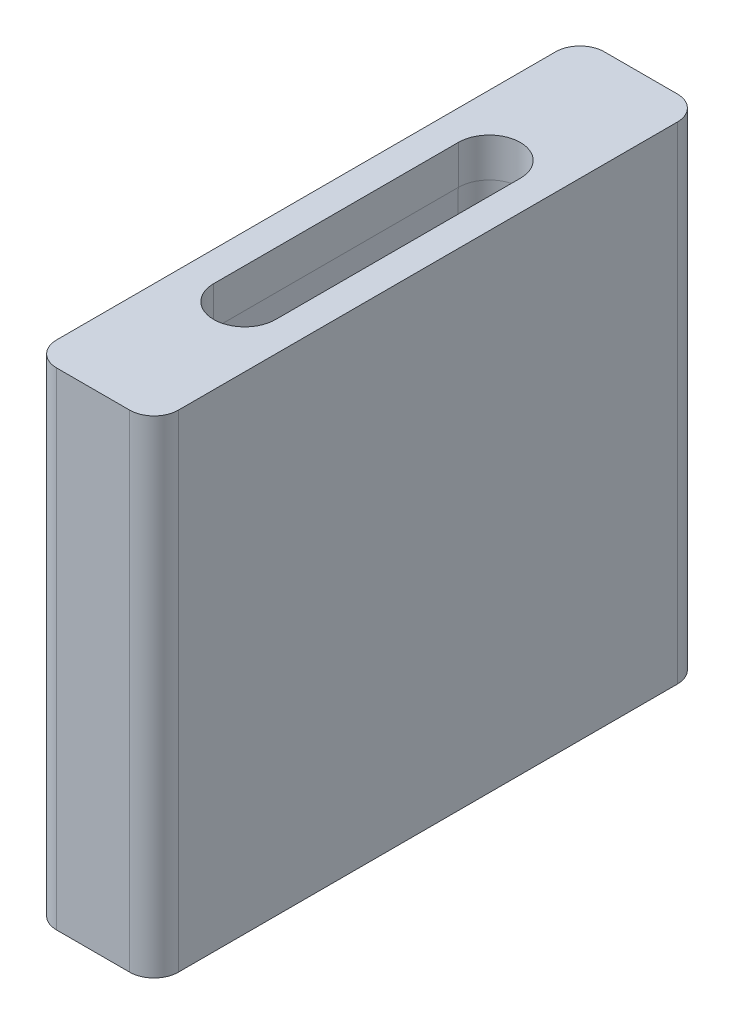
SolidWorks part; units mm, degrees
material "K110"
ref_plane "Front Plane" through (0, 0, 0) normal (0, 0, 1) x (1, 0, 0)
ref_plane "Top Plane" through (0, 0, 0) normal (0, 1, 0) x (1, 0, 0)
ref_plane "Right Plane" through (0, 0, 0) normal (1, 0, 0) x (0, 0, -1)
sketch "Sketch1" plane through (0, 0, 0) normal (0, 1, 0) x (1, 0, 0)
  line L3 (0, -3.5) -> (0, 3.5) construction
  line L4 (-2.62, -3.5) -> (-2.62, 3.5) construction
  line L5 (2.62, -3.5) -> (2.62, 3.5) construction
  line L6 (-3, -22.5) -> (3, -22.5)
  line L7 (-5, -20.5) -> (-5, 20.5)
  line L8 (-3, 22.5) -> (3, 22.5)
  line L9 (5, -20.5) -> (5, 20.5)
  line L10 (-5, -22.5) -> (5, 22.5) construction
  line L11 (-5, 22.5) -> (5, -22.5) construction
  arc A2 (-2.62, -3.5) -> (2.62, -3.5) centre (0, -3.5) ccw construction
  arc A3 (2.62, 3.5) -> (-2.62, 3.5) centre (0, 3.5) ccw construction
  arc A4 (-3, -22.5) -> (-5, -20.5) centre (-3, -20.5) cw
  arc A5 (3, -22.5) -> (5, -20.5) centre (3, -20.5) ccw
  arc A6 (3, 22.5) -> (5, 20.5) centre (3, 20.5) cw
  arc A7 (-5, 20.5) -> (-3, 22.5) centre (-3, 20.5) cw
  point P0 (0, 0)
  point P10 (0, 0)
  dimension "D1" = 7
  dimension "D3" = 2.62
  dimension "D5" = 2
  dimension "D2" = 45
  dimension "D4" = 10
extrude "Boss-Extrude1" add sketch "Sketch1" against normal blind 40
sketch "Sketch5" plane through (0, 0, 0) normal (0, 1, 0) x (1, 0, 0)
  line L0 (0, -10.05) -> (0, 10.05) construction
  line L1 (-2.55, -10.05) -> (-2.55, 10.05)
  line L2 (2.55, -10.05) -> (2.55, 10.05)
  arc A0 (-2.55, -10.05) -> (2.55, -10.05) centre (0, -10.05) ccw
  arc A1 (2.55, 10.05) -> (-2.55, 10.05) centre (0, 10.05) ccw
  point P4 (0, 0)
  dimension "D1" = 20.1
  dimension "D2" = 5.1
extrude "Cut-Extrude2" cut sketch "Sketch5" against normal up to next
sketch "Sketch7" plane through (0, 0, 0) normal (0, 0, 1) x (1, 0, 0)
  line L0 (2.55, -3.2) -> (3.1923, -40)
  line L1 (2.55, -40) -> (2.55, 0) construction
  line L2 (-3, -40) -> (3, -40) construction
  line L3 (3.1923, -40) -> (2.55, -40)
  line L4 (2.55, -40) -> (2.55, -3.2)
  line L5 (5, 0) -> (3, 0) construction
  dimension "D1" = 3.2
  dimension "D2" = 1
sketch "Sketch8" plane through (0, 0, 0) normal (0, 1, 0) x (1, 0, 0)
  line L0 (-2.55, 10.05) -> (-2.55, -10.05) construction
  line L1 (2.55, -10.05) -> (2.55, 10.05) construction
  line L2 (-2.55, 10.05) -> (-2.55, -10.05)
  line L3 (2.55, -10.05) -> (2.55, 10.05)
  arc A0 (2.55, 10.05) -> (-2.55, 10.05) centre (0, 10.05) ccw construction
  arc A1 (-2.55, -10.05) -> (2.55, -10.05) centre (0, -10.05) ccw construction
  arc A2 (2.55, 10.05) -> (-2.55, 10.05) centre (0, 10.05) ccw
  arc A3 (-2.55, -10.05) -> (2.55, -10.05) centre (0, -10.05) ccw
sweep "Cut-Sweep1" cut profiles "Sketch7" path "Sketch8"
hole_wizard "M6 Tapped Hole1" positions "Sketch11" profile "Sketch10" tap size "M6" standard "ISO"
sketch "Sketch11" plane through (0, -40, 0) normal (0, -1, 0) x (-1, 0, 0)
  line L0 (-3, 22.5) -> (3, 22.5) construction
  line L5 (3, -22.5) -> (-3, -22.5) construction
  line L6 (0, 22.5) -> (0, -22.5) construction
  point P0 (0, 17.5)
  point P2 (0, -17.5)
  dimension "D1" = 5
  dimension "D4" = 5
sketch "Sketch10" plane through (0, -40, -17.5) normal (1, 0, 0) x (0, 0, -1)
  line L0 (0, 0) -> (0, 18.5022)
  line L1 (0, 18.5022) -> (2.5, 17)
  line L2 (2.5, 17) -> (2.5, 0.525)
  line L3 (2.5, 0.525) -> (3.025, 0)
  line L5 (3.025, 0) -> (0, 0)
  line L6 (-2.5, 0.525) -> (-3.025, 0) construction
  line L10 (0, 18.5022) -> (-2.5, 17) construction
  line L11 (0, -6.35) -> (0, 107.95) construction
  dimension "Tap Drill Dia." = 5
  dimension "Tap Drill Depth" = 17
  dimension "Near C'Sink Dia." = 6.05
  dimension "Near C'Sink Angle" = 90
  dimension "Drill Angle" = 118
cosmetic thread "Hole Thread1"
cosmetic thread "Hole Thread2"
